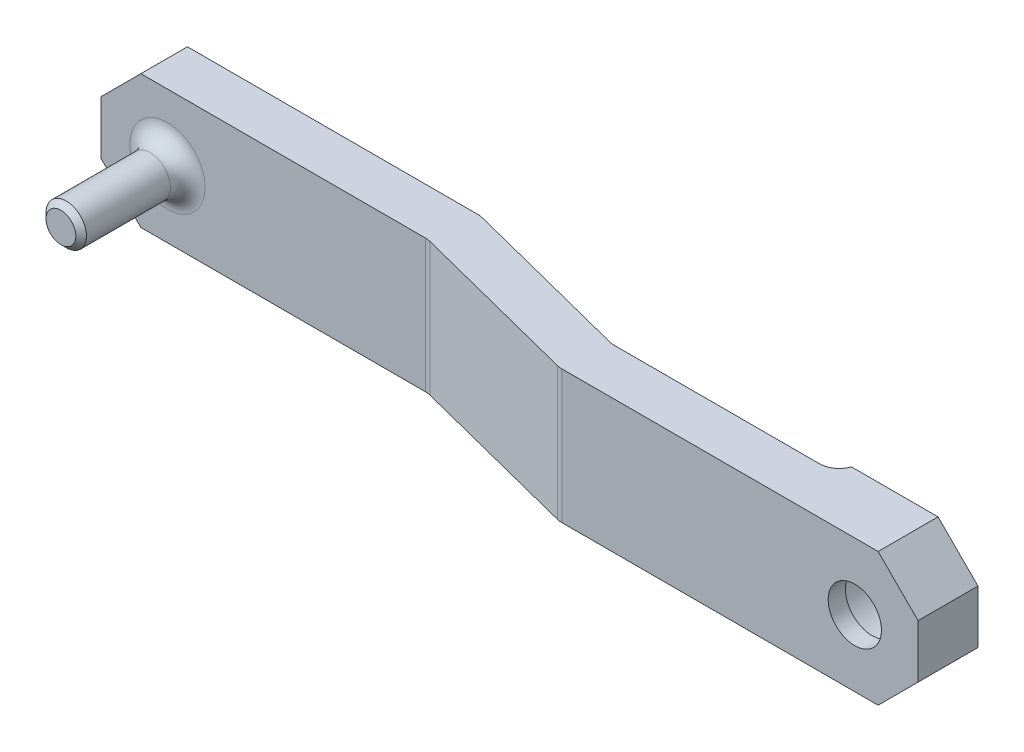
SolidWorks part; units mm, degrees
material "PLA"
ref_plane "Front Plane" through (0, 0, 0) normal (0, 0, 1) x (1, 0, 0)
ref_plane "Top Plane" through (0, 0, 0) normal (0, 1, 0) x (1, 0, 0)
ref_plane "Right Plane" through (0, 0, 0) normal (1, 0, 0) x (0, 0, -1)
sketch "Sketch1" plane through (0, 0, 0) normal (0, 1, 0) x (1, 0, 0)
  line L0 (0, 0) -> (0, -4.445)
  line L1 (0, -4.445) -> (31.1907, -4.445)
  line L2 (31.1907, -4.445) -> (48.0182, -8.7475)
  line L3 (48.0182, -8.7475) -> (82.2325, -8.7475)
  line L4 (82.2325, -8.7475) -> (82.2325, -3.0325)
  line L5 (82.2325, -3.0325) -> (70.1675, -3.0325)
  line L6 (70.1675, -3.0325) -> (70.1675, -4.3025)
  line L7 (70.1675, -4.3025) -> (48.5775, -4.3025)
  line L8 (48.5775, -4.3025) -> (31.75, 0)
  line L9 (31.75, 0) -> (0, 0)
  line L10 (76.2, -3.0325) -> (76.2, -6.0325) construction
  line L11 (6.35, 0) -> (6.35, -4.445) construction
  line L12 (100.0125, -6.0325) -> (76.2, -6.0325) construction
  line L13 (0, -2.2225) -> (6.35, -2.2225) construction
  dimension "D1" = 12.065
  dimension "D2" = 6.35
  dimension "D3" = 69.85
  dimension "D4" = 3.81
  dimension "D5" = 5.715
  dimension "D6" = 4.445
  dimension "D7" = 4.445
  dimension "D8" = 4.445
  dimension "D9" = 31.75
  dimension "D10" = 21.59
  dimension "D11" = 3
extrude "Boss-Extrude1" add sketch "Sketch1" along normal blind 12.7
sketch "Sketch2" plane through (0, 0, 3.0325) normal (0, 0, -1) x (-1, 0, 0)
  line L0 (-76.2, 12.7) -> (-76.2, 0) construction
  line L1 (-82.2325, 12.7) -> (-70.1675, 12.7) construction
  line L2 (-82.2325, 0) -> (-70.1675, 0) construction
  circle A0 centre (-76.2, 6.35) radius 4.1148
  dimension "D1" = 8.2296
extrude "Cut-Extrude1" cut sketch "Sketch2" against normal blind 4.064
sketch "Sketch3" plane through (0, 0, 7.0965) normal (0, 0, -1) x (-1, 0, 0)
  circle A0 centre (-76.2, 6.35) radius 2.54
  dimension "D1" = 5.08
extrude "Cut-Extrude2" cut sketch "Sketch3" against normal through all
sketch "Sketch4" plane through (0, 0, 4.445) normal (0, 0, -1) x (-1, 0, 0)
  line L0 (0, 6.35) -> (-6.35, 6.35) construction
  line L1 (0, 12.7) -> (0, 0) construction
  circle A0 centre (-6.35, 6.35) radius 1.9304
  dimension "D2" = 3.8608
  dimension "D1" = 6.35
extrude "Boss-Extrude2" add sketch "Sketch4" against normal blind 10.16
fillet "Fillet1" radius 1.651 1 edges at (4.4196, 6.35, 4.445)
chamfer "Chamfer1" distance 3.81 angle 45 4 edges at (82.2325, 0, 5.89) (82.2325, 12.7, 5.89) (0, 0, 2.2225) (0, 12.7, 2.2225)
fillet "Fillet2" radius 1.905 5 edges at (48.0182, 6.35, 8.7475) (31.1907, 6.35, 4.445) (31.75, 6.35, 0) (48.5775, 6.35, 4.3025) (70.1675, 6.35, 4.3025)
chamfer "Chamfer2" distance 0.635 angle 45 1 edges at (72.0852, 6.35, 3.0325)
chamfer "Chamfer3" distance 0.508 angle 45 1 edges at (4.4196, 6.35, 14.605)
